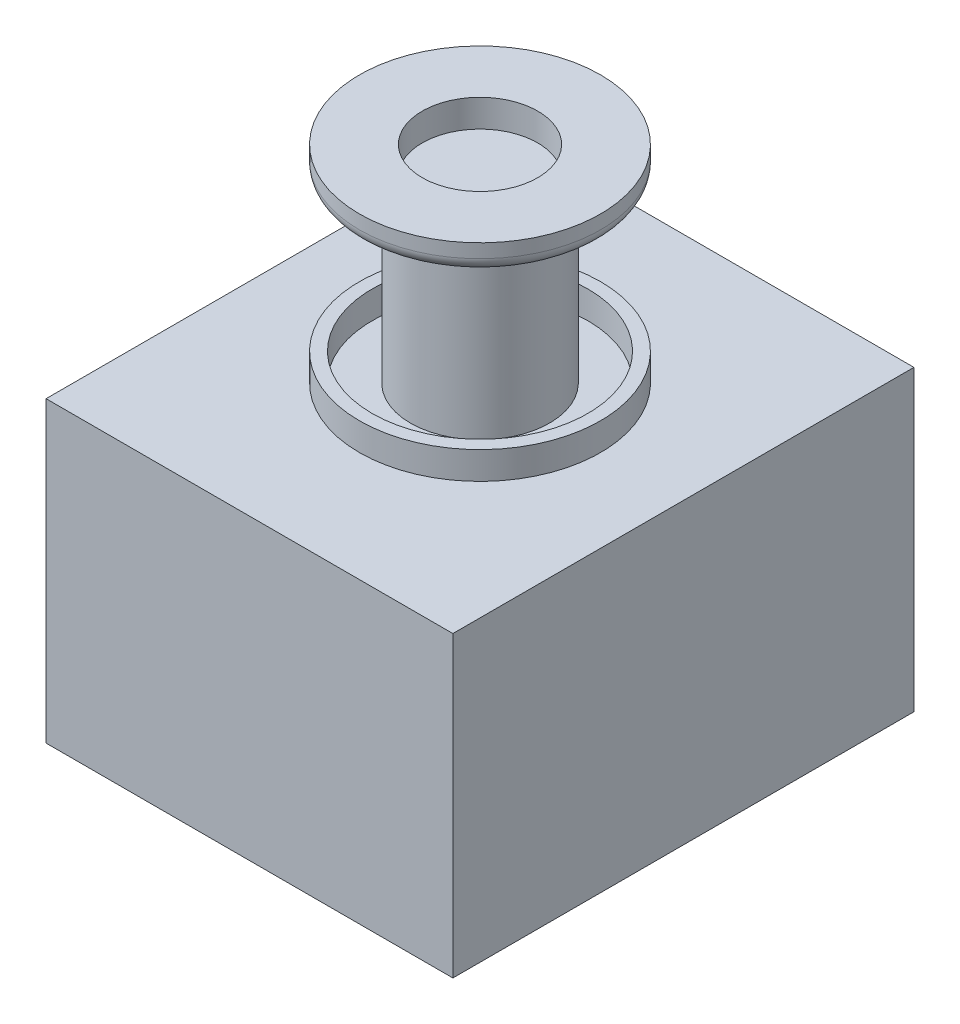
SolidWorks part; units mm, degrees
ref_plane "Front Plane" through (0, 0, 0) normal (0, 0, 1) x (1, 0, 0)
ref_plane "Top Plane" through (0, 0, 0) normal (0, 1, 0) x (1, 0, 0)
ref_plane "Right Plane" through (0, 0, 0) normal (1, 0, 0) x (0, 0, -1)
sketch "Sketch1" plane through (0, 0, 0) normal (0, 1, 0) x (1, 0, 0)
  line L1 (-37.5, 42.5) -> (37.5, 42.5)
  line L2 (-37.5, 42.5) -> (-37.5, -42.5)
  line L3 (-37.5, -42.5) -> (37.5, -42.5)
  line L4 (37.5, 42.5) -> (37.5, -42.5)
  line L5 (-37.5, 42.5) -> (37.5, -42.5) construction
  line L6 (-37.5, -42.5) -> (37.5, 42.5) construction
  point P0 (0, 0)
  dimension "D1" = 85
extrude "Boss-Extrude1" add sketch "Sketch1" along normal blind 55
sketch "Sketch2" plane through (0, 55, 0) normal (0, 1, 0) x (1, 0, 0)
  circle A0 centre (0, 0) radius 22.225
extrude "Boss-Extrude2" add sketch "Sketch2" along normal blind 5.08
sketch "Sketch3" plane through (0, 60.08, 0) normal (0, 1, 0) x (1, 0, 0)
  circle A0 centre (0, 0) radius 19.8906
extrude "Boss-Extrude3" [suppressed] add sketch "Sketch3" against normal blind 5.08
extrude "Cut-Extrude1" cut sketch "Sketch3<2>" against normal blind 5.08
sketch "Sketch3<2>" plane through (0, 60.08, 0) normal (0, 1, 0) x (1, 0, 0) same geometry as "Sketch3"
sketch "Sketch4" plane through (0, 55, 0) normal (0, 1, 0) x (1, 0, 0)
  circle A0 centre (0, 0) radius 12.8197
extrude "Boss-Extrude4" add sketch "Sketch4" along normal blind 33.02
sketch "Sketch5" plane through (0, 88.02, 0) normal (0, 1, 0) x (1, 0, 0)
  circle A0 centre (0, 0) radius 22.225
extrude "Boss-Extrude5" add sketch "Sketch5" along normal blind 5.08
fillet "Fillet1" radius 2.54 2 edges at (0, 88.02, 22.225) (0, 88.02, 12.8197)
sketch "Sketch6" plane through (0, 93.1, 0) normal (0, 1, 0) x (1, 0, 0)
  circle A0 centre (0, 0) radius 10.6451
extrude "Cut-Extrude2" cut sketch "Sketch6" against normal blind 5.08
